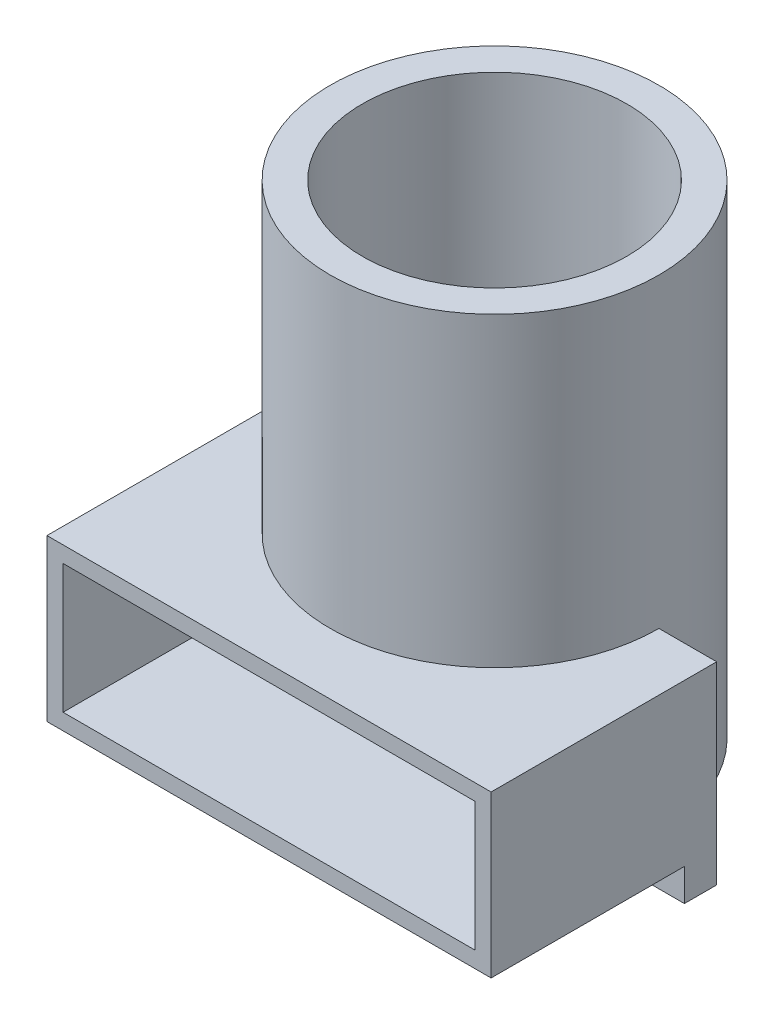
SolidWorks part; units mm, degrees
ref_plane "前基準面" through (0, 0, 0) normal (0, 0, 1) x (1, 0, 0)
ref_plane "上基準面" through (0, 0, 0) normal (0, 1, 0) x (1, 0, 0)
ref_plane "右基準面" through (0, 0, 0) normal (1, 0, 0) x (0, 0, -1)
sketch "要刪除的圖檔" plane through (0, 0, 0) normal (0, 1, 0) x (1, 0, 0)
  circle A0 centre (0, 0) radius 350.139 construction
  dimension "D1" = 700.278
sketch "草圖2" plane through (0, 0, 0) normal (0, 1, 0) x (1, 0, 0)
  circle A0 centre (0, 0) radius 259.207
  dimension "D1" = 518.414
extrude "主件固定 19mm" add sketch "草圖2" along normal blind 482.6 thin thin type one direction reverse wall 50.8
sketch "草圖3" plane through (0, 0, 0) normal (0, 1, 0) x (1, 0, 0)
  line L0 (-1000, 0) -> (49000, 0) construction
  arc A0 (208.407, 0) -> (-208.407, 0) centre (0, 0) ccw
extrude "下填充 11mm" add sketch "草圖3" against normal blind 279.4 thin thin type one direction wall 50.8
sketch "草圖8" plane through (0, 0, 0) normal (0, 0, 1) x (1, 0, 0)
  line L0 (350.139, 0) -> (-350.139, 0) construction
  line L1 (-350.139, 0) -> (350.139, 0)
  line L2 (-350.139, 0) -> (-350.139, -254)
  line L3 (-350.139, -254) -> (350.139, -254)
  line L4 (350.139, 0) -> (350.139, -254)
extrude "填料-伸長2" add sketch "草圖8" along normal blind 355.6
sketch "草圖11" plane through (0, 0, 355.6) normal (0, 0, 1) x (1, 0, 0)
  line L0 (350.139, 0) -> (-350.139, 0) construction
  line L1 (-324.739, -25.4) -> (324.739, -25.4)
  line L2 (-324.739, -25.4) -> (-324.739, -228.6)
  line L3 (-324.739, -228.6) -> (324.739, -228.6)
  line L4 (324.739, -25.4) -> (324.739, -228.6)
  line L5 (-350.139, -254) -> (350.139, -254) construction
  line L6 (-350.139, 0) -> (-350.139, -254) construction
  line L7 (350.139, -254) -> (350.139, 0) construction
  dimension "D1" = 25.4
  dimension "D2" = 25.4
  dimension "D3" = 25.4
  dimension "D4" = 25.4
extrude "除料-伸長1" cut sketch "草圖11" against normal blind 279.4
fillet "圓角2" radius 127 1 edges at (0, 0, 0)
sketch "草圖13" plane through (0, -254, 0) normal (0, -1, 0) x (1, 0, 0)
  line L0 (-350.139, 0) -> (-259.207, 0) construction
  line L1 (-350.139, 0) -> (350.139, 0)
  line L2 (-350.139, 0) -> (-350.139, 50.8)
  line L3 (-350.139, 50.8) -> (350.139, 50.8)
  line L4 (350.139, 0) -> (350.139, 50.8)
  line L5 (350.139, 355.6) -> (350.139, 0) construction
  circle A0 centre (0, 0) radius 350.139 construction
  dimension "D1" = 50.8
extrude "防水凸出2mm" add sketch "草圖13" along normal blind 50.8
